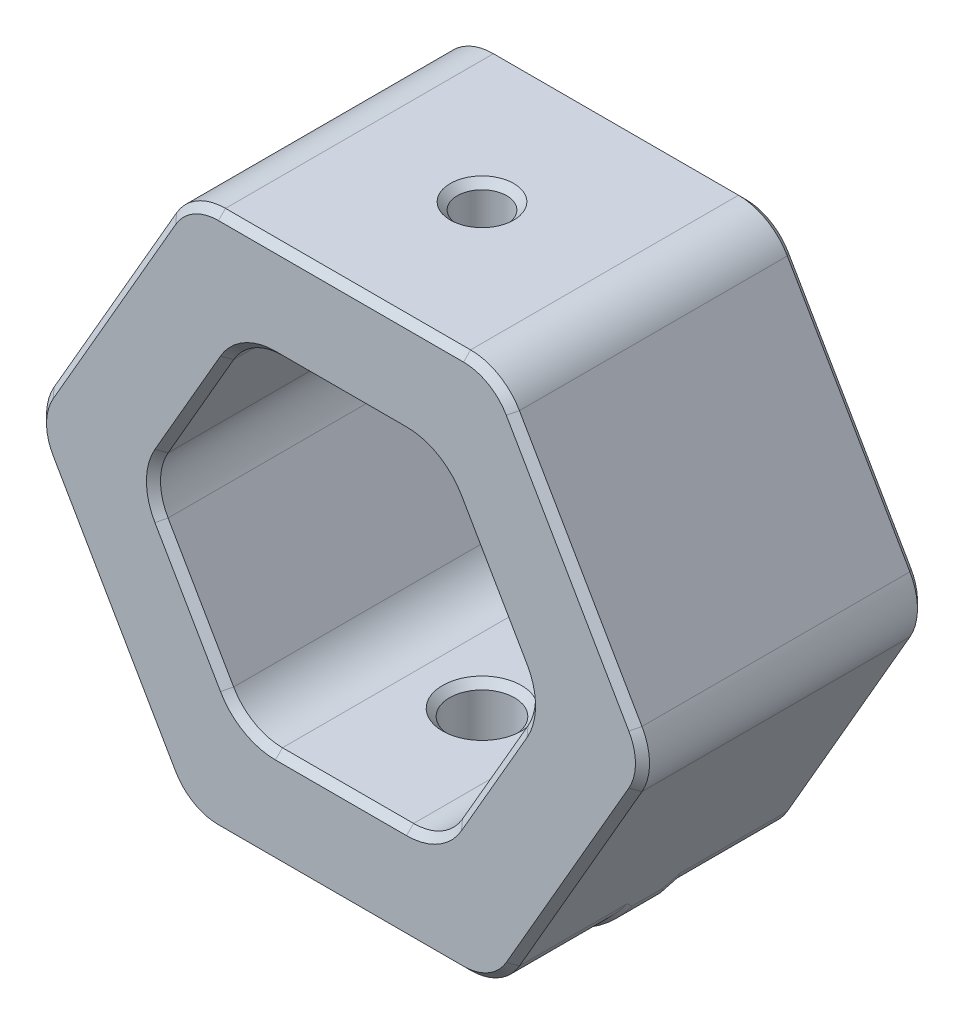
SolidWorks part; units mm, degrees
ref_plane "Front" through (0, 0, 0) normal (0, 0, 1) x (1, 0, 0)
ref_plane "Top" through (0, 0, 0) normal (0, 1, 0) x (1, 0, 0)
ref_plane "Right" through (0, 0, 0) normal (1, 0, 0) x (0, 0, -1)
sketch "Skizze1" plane through (0, 0, 0) normal (0, 0, 1) x (1, 0, 0)
  line L0 (-11, 0) -> (11, 0)
  line L1 (0, 0) -> (0, 41.7081) construction
  line L2 (11, 0) -> (22, 19.0526)
  line L3 (22, 19.0526) -> (11, 38.1051)
  line L4 (11, 38.1051) -> (-11, 38.1051)
  line L5 (-22, 19.0526) -> (-11, 38.1051)
  line L6 (-11, 0) -> (-22, 19.0526)
  line L7 (0, 7) -> (6.9585, 7)
  line L8 (6.9585, 7) -> (13.9171, 19.0526)
  line L9 (13.9171, 19.0526) -> (6.9585, 31.1051)
  line L10 (6.9585, 31.1051) -> (-6.9585, 31.1051)
  line L11 (-6.9585, 31.1051) -> (-13.9171, 19.0526)
  line L12 (-13.9171, 19.0526) -> (-6.9585, 7)
  line L13 (-6.9585, 7) -> (0, 7)
  dimension "D1" = 22
  dimension "D2" = 120
  dimension "D3" = 120
  dimension "D4" = 7
  dimension "D5" = 7
  dimension "D6" = 7
  dimension "D7" = 7
  dimension "D8" = 7
  dimension "D9" = 7
extrude "Aufsatz-Linear austragen1" add sketch "Skizze1" along normal blind 20
sketch "Skizze3" plane through (0, 0, 0) normal (1, 0, 0) x (0, 0, -1)
  line L0 (-10, 0) -> (-10, -13.6655) construction
  line L1 (-20, 0) -> (0, 0) construction
  line L2 (-13.5, 0) -> (-6.5, 0)
  line L3 (-6.5, 0) -> (-7.25, -0.75)
  line L4 (-7.25, -0.75) -> (-12.75, -0.75)
  line L5 (-13.5, 0) -> (-12.75, -0.75)
  point P8 (-10, -0.75)
  dimension "D1" = 7
  dimension "D2" = 0.75
  dimension "D3" = 45
extrude "Aufsatz-Linear austragen2" add sketch "Skizze3" along normal up to surface and the other way up to surface up to face at (16.5, 9.5263, 10) other way up to face at (-16.5, 9.5263, 10)
sketch "Skizze2" plane through (0, 7, 0) normal (0, 1, 0) x (1, 0, 0)
  line L0 (-6.9585, -10) -> (6.9585, -10) construction
  line L1 (-6.9585, -20) -> (-6.9585, 0) construction
  line L2 (6.9585, -20) -> (6.9585, 0) construction
  circle A0 centre (0, -10) radius 2.3
  dimension "D1" = 4.6
extrude "Schnitt-Linear austragen1" cut sketch "Skizze2" against normal blind 20
sketch "Skizze4" plane through (0, 0, 0) normal (0, -1, 0) x (1, 0, 0)
  circle A0 centre (0, 10) radius 4.2
  dimension "D1" = 8.4
extrude "Schnitt-Linear austragen2" cut sketch "Skizze4" along normal blind 20
fillet "Verrundung1" radius 0.75 2 edges at (-4.2, -0.75, 10) (4.2, -0.75, 10)
fillet "Verrundung2" radius 4 20 edges at (22, 19.0526, 10) (11, 38.1051, 10) (-11, 38.1051, 10) (-22, 19.0526, 10) (13.9171, 19.0526, 10) (6.9585, 7, 10) (-6.9585, 7, 10) (-13.9171, 19.0526, 10) (-6.9585, 31.1051, 10) (6.9585, 31.1051, 10) (-10.7835, -0.375, 6.875) (10.7835, -0.375, 6.875) (11, 0, 3.25) (10.567, -0.75, 10) (-10.567, -0.75, 10) (10.7835, -0.375, 13.125) (-10.7835, -0.375, 13.125) (11, 0, 16.75) (-11, 0, 3.25) (-11, 0, 16.75)
sketch "Skizze5" plane through (0, 31.1051, 0) normal (0, -1, 0) x (1, 0, 0)
  circle A0 centre (0, 10) radius 1.75
  dimension "D1" = 3.5
extrude "Schnitt-Linear austragen3" cut sketch "Skizze5" against normal blind 20
chamfer "Fase1" distance 0.5 angle 45 52 edges at (-13.2983, 19.0526, 0) (-10.4378, 25.0788, 0) (-6.6491, 30.5692, 0) (0, 31.1051, 0) (6.6491, 30.5692, 0) (10.4378, 25.0788, 0) (13.2983, 19.0526, 0) (10.4378, 13.0263, 0) (6.6491, 7.5359, 0) (0, 7, 0) (-6.6491, 7.5359, 0) (-10.4378, 13.0263, 0) (21.3812, 19.0526, 0) (16.5, 28.5788, 0) (10.6906, 37.5692, 0) (0, 38.1051, 0) (-10.6906, 37.5692, 0) (-16.5, 28.5788, 0) (-21.3812, 19.0526, 0) (-16.5, 9.5263, 0) (-10.6906, 0.5359, 0) (0, 0, 0) (10.6906, 0.5359, 0) (16.5, 9.5263, 0) (13.2983, 19.0526, 20) (10.4378, 25.0788, 20) (6.6491, 30.5692, 20) (0, 31.1051, 20) (-6.6491, 30.5692, 20) (-10.4378, 25.0788, 20) (-13.2983, 19.0526, 20) (-10.4378, 13.0263, 20) (-6.6491, 7.5359, 20) (0, 7, 20) (6.6491, 7.5359, 20) (10.4378, 13.0263, 20) (-10.6906, 0.5359, 20) (-16.5, 9.5263, 20) (-21.3812, 19.0526, 20) (-16.5, 28.5788, 20) (-10.6906, 37.5692, 20) (0, 38.1051, 20) (10.6906, 37.5692, 20) (16.5, 28.5788, 20) (21.3812, 19.0526, 20) (16.5, 9.5263, 20) (10.6906, 0.5359, 20) (0, 0, 20) (0, 0, 7.7) (0, 7, 12.3) (0, 38.1051, 8.25) (0, 31.1051, 8.25)
